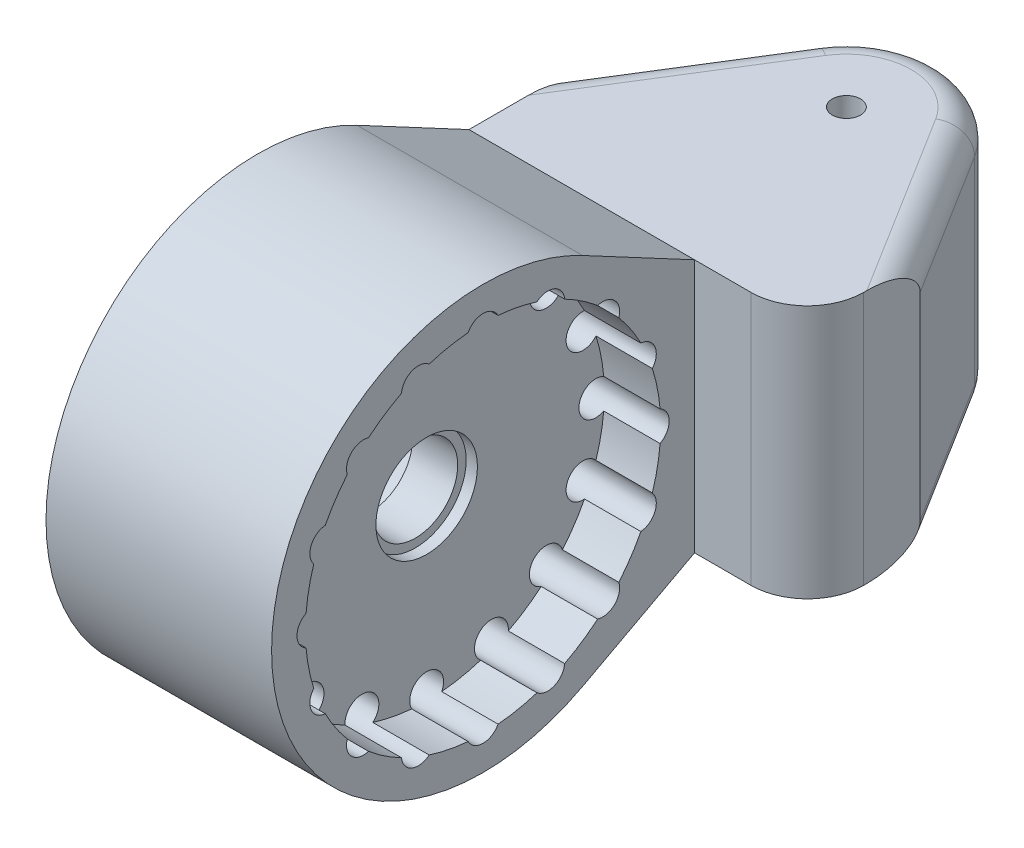
SolidWorks part; units mm, degrees
material "ABS"
ref_plane "Front Plane" through (0, 0, 0) normal (0, 0, 1) x (1, 0, 0)
ref_plane "Top Plane" through (0, 0, 0) normal (0, 1, 0) x (1, 0, 0)
ref_plane "Right Plane" through (0, 0, 0) normal (1, 0, 0) x (0, 0, -1)
ref_plane "Plane1" through (0, 0, 36.9266) normal (0, 0, 1) x (1, 0, 0)
sketch "Sketch1" plane through (0, 0, 0) normal (0, 0, 1) x (1, 0, 0)
  line L1 (-30, 22.5) -> (30, 22.5)
  line L2 (-30, 22.5) -> (-30, -22.5)
  line L3 (-30, -22.5) -> (30, -22.5)
  line L4 (30, 22.5) -> (30, -22.5)
  line L5 (-30, 22.5) -> (30, -22.5) construction
  line L6 (-30, -22.5) -> (30, 22.5) construction
  point P0 (0, 0)
  dimension "D1" = 45
  dimension "D2" = 60
extrude "Boss-Extrude1" add sketch "Sketch1" along normal blind 20 from surface at 36.9266 starting at plane "Plane1"
sketch "Sketch2" plane through (0, 0, 56.9266) normal (0, 0, 1) x (1, 0, 0)
  line L0 (-30, 22.5) -> (30, 22.5) construction
  line L1 (-30, -22.5) -> (0, -22.5)
  line L2 (-30, -22.5) -> (-30, 22.5)
  line L3 (-30, 22.5) -> (0, 22.5)
  line L4 (0, -22.5) -> (0, 22.5)
extrude "Boss-Extrude2" add sketch "Sketch2" along normal blind 75
sketch "Sketch4" plane through (0, -22.5, 0) normal (0, -1, 0) x (1, 0, 0)
  line L0 (30, 36.9266) -> (-30, 36.9266) construction
  line L1 (-30, 36.9266) -> (-14.001, 11.2694)
  line L2 (30, 36.9266) -> (14.001, 11.2694)
  line L3 (-30, 36.9266) -> (30, 36.9266)
  arc A0 (-14.001, 11.2694) -> (14.001, 11.2694) centre (0, 20) ccw
  circle A1 centre (0, 20) radius 2.5
  dimension "D2" = 5
  dimension "D3" = 16.5
  dimension "D1" = 16.9266
extrude "Boss-Extrude3" add sketch "Sketch4" against normal up to surface (45 mm away) up to face at (0, 22.5, 75.2599)
fillet "Fillet1" radius 5 6 edges at (-22.0005, 22.5, 24.098) (-22.0005, -22.5, 24.098) (22.0005, 22.5, 24.098) (22.0005, -22.5, 24.098) (0, 22.5, 3.5) (0, -22.5, 3.5)
sketch "Sketch5" plane through (0, 0, 0) normal (1, 0, 0) x (0, 0, -1)
  line L0 (-94.4266, -22.5) -> (-94.4266, 22.5) construction
  line L1 (-131.9266, -22.5) -> (-56.9266, -22.5) construction
  line L2 (-131.9266, 22.5) -> (-56.9266, 22.5) construction
  line L3 (-56.9266, -22.5) -> (-56.9266, 22.5) construction
  line L4 (-56.9266, -22.5) -> (-76.7795, -33.0882)
  line L5 (-76.7795, 33.0882) -> (-56.9266, 22.5)
  line L6 (-56.9266, -22.5) -> (-56.9266, 22.5)
  arc A0 (-76.7795, 33.0882) -> (-76.7795, -33.0882) centre (-94.4266, 0) ccw
  dimension "D1" = 37.5
extrude "Boss-Extrude4" add sketch "Sketch5" against normal through all
sketch "Sketch6" plane through (0, 0, 0) normal (1, 0, 0) x (0, 0, -1)
  line L0 (-94.4266, -43.7321) -> (-94.4266, -37.5)
  line L1 (-94.4266, 37.5) -> (-94.4266, 43.7321)
  arc A1 (-94.4266, 43.7321) -> (-94.4266, -43.7321) centre (-94.4266, 0) ccw
  arc A2 (-124.4266, -22.5) -> (-76.7795, -33.0882) centre (-94.4266, 0) ccw construction
  arc A3 (-124.4266, -22.5) -> (-94.4266, -37.5) centre (-94.4266, 0) ccw construction
  arc A4 (-94.4266, 37.5) -> (-94.4266, -37.5) centre (-94.4266, 0) ccw
extrude "Cut-Extrude1" cut sketch "Sketch6" against normal up to next
sketch "Sketch9" plane through (0, 0, 0) normal (1, 0, 0) x (0, 0, -1)
  line L3 (-76.7795, -33.0882) -> (-56.9266, -22.5)
  line L4 (-56.9266, -22.5) -> (-56.9266, 22.5)
  line L5 (-56.9266, 22.5) -> (-76.7795, 33.0882)
  line L6 (-76.7795, -33.0882) -> (-56.9266, -22.5) construction
  line L7 (-56.9266, -22.5) -> (-56.9266, 22.5) construction
  line L8 (-56.9266, 22.5) -> (-76.7795, 33.0882) construction
  circle A0 centre (-94.4266, 0) radius 30 construction
  arc A1 (-76.7795, 33.0882) -> (-76.7795, -33.0882) centre (-94.4266, 0) ccw
  arc A2 (-76.7795, 33.0882) -> (-76.7795, -33.0882) centre (-94.4266, 0) ccw construction
  circle A3 centre (-94.4266, -30) radius 3
  circle A4 centre (-105.9071, -27.7164) radius 3
  circle A5 centre (-115.6398, -21.2132) radius 3
  circle A6 centre (-122.143, -11.4805) radius 3
  circle A7 centre (-124.4266, 0) radius 3
  circle A8 centre (-122.143, 11.4805) radius 3
  circle A9 centre (-115.6398, 21.2132) radius 3
  circle A10 centre (-105.9071, 27.7164) radius 3
  circle A11 centre (-94.4266, 30) radius 3
  circle A12 centre (-82.9461, 27.7164) radius 3
  circle A13 centre (-73.2134, 21.2132) radius 3
  circle A14 centre (-66.7102, 11.4805) radius 3
  circle A15 centre (-64.4266, 0) radius 3
  circle A16 centre (-66.7102, -11.4805) radius 3
  circle A17 centre (-73.2134, -21.2132) radius 3
  circle A18 centre (-82.9461, -27.7164) radius 3
  point P39 (-94.4266, 0)
  dimension "D2" = 6
  dimension "D4" = 60
extrude "Cut-Extrude2" cut sketch "Sketch9" against normal blind 10
sketch "Sketch10" plane through (0, 0, 0) normal (1, 0, 0) x (0, 0, -1)
  line L3 (-76.7795, -33.0882) -> (-56.9266, -22.5)
  line L4 (-56.9266, -22.5) -> (-56.9266, 22.5)
  line L5 (-56.9266, 22.5) -> (-76.7795, 33.0882)
  line L6 (-76.7795, -33.0882) -> (-56.9266, -22.5)
  line L7 (-56.9266, -22.5) -> (-56.9266, 22.5)
  line L8 (-56.9266, 22.5) -> (-76.7795, 33.0882)
  arc A1 (-79.9577, -27.9804) -> (-74.1131, -24.0751) centre (-94.4266, 0) ccw
  arc A2 (-76.7795, 33.0882) -> (-76.7795, -33.0882) centre (-94.4266, 0) ccw construction
  arc A3 (-108.8955, -27.9804) -> (-103.9807, -30.0162) centre (-105.9071, -27.7164) ccw
  circle A4 centre (-94.4266, -30) radius 3
  arc A5 (-97.0864, -31.3875) -> (-91.7667, -31.3875) centre (-94.4266, -30) ccw
  arc A6 (-118.5017, -20.3135) -> (-114.7401, -24.0751) centre (-115.6398, -21.2132) ccw
  arc A7 (-124.4427, -9.5541) -> (-122.407, -14.4689) centre (-122.143, -11.4805) ccw
  arc A8 (-125.8141, 2.6599) -> (-125.8141, -2.6599) centre (-124.4266, 0) ccw
  arc A9 (-122.407, 14.4689) -> (-124.4427, 9.5541) centre (-122.143, 11.4805) ccw
  arc A10 (-114.7401, 24.0751) -> (-118.5017, 20.3135) centre (-115.6398, 21.2132) ccw
  arc A11 (-103.9807, 30.0162) -> (-108.8955, 27.9804) centre (-105.9071, 27.7164) ccw
  arc A12 (-91.7667, 31.3875) -> (-97.0864, 31.3875) centre (-94.4266, 30) ccw
  arc A13 (-79.9577, 27.9804) -> (-84.8725, 30.0162) centre (-82.9461, 27.7164) ccw
  arc A14 (-70.3515, 20.3135) -> (-74.1131, 24.0751) centre (-73.2134, 21.2132) ccw
  arc A15 (-64.4104, 9.5541) -> (-66.4462, 14.4689) centre (-66.7102, 11.4805) ccw
  arc A16 (-63.0391, -2.6599) -> (-63.0391, 2.6599) centre (-64.4266, 0) ccw
  arc A17 (-66.4462, -14.4689) -> (-64.4104, -9.5541) centre (-66.7102, -11.4805) ccw
  arc A18 (-74.1131, -24.0751) -> (-70.3515, -20.3135) centre (-73.2134, -21.2132) ccw
  arc A19 (-84.8725, -30.0162) -> (-79.9577, -27.9804) centre (-82.9461, -27.7164) ccw
  arc A20 (-91.7667, -31.3875) -> (-84.8725, -30.0162) centre (-94.4266, 0) ccw
  arc A21 (-103.9807, -30.0162) -> (-97.0864, -31.3875) centre (-94.4266, 0) ccw
  arc A22 (-114.7401, -24.0751) -> (-108.8955, -27.9804) centre (-94.4266, 0) ccw
  arc A23 (-122.407, -14.4689) -> (-118.5017, -20.3135) centre (-94.4266, 0) ccw
  arc A24 (-125.8141, -2.6599) -> (-124.4427, -9.5541) centre (-94.4266, 0) ccw
  arc A25 (-124.4427, 9.5541) -> (-125.8141, 2.6599) centre (-94.4266, 0) ccw
  arc A26 (-118.5017, 20.3135) -> (-122.407, 14.4689) centre (-94.4266, 0) ccw
  arc A27 (-108.8955, 27.9804) -> (-114.7401, 24.0751) centre (-94.4266, 0) ccw
  arc A28 (-97.0864, 31.3875) -> (-103.9807, 30.0162) centre (-94.4266, 0) ccw
  arc A29 (-84.8725, 30.0162) -> (-91.7667, 31.3875) centre (-94.4266, 0) ccw
  arc A30 (-74.1131, 24.0751) -> (-79.9577, 27.9804) centre (-94.4266, 0) ccw
  arc A31 (-66.4462, 14.4689) -> (-70.3515, 20.3135) centre (-94.4266, 0) ccw
  arc A32 (-63.0391, 2.6599) -> (-64.4104, 9.5541) centre (-94.4266, 0) ccw
  arc A33 (-64.4104, -9.5541) -> (-63.0391, -2.6599) centre (-94.4266, 0) ccw
  arc A34 (-70.3515, -20.3135) -> (-66.4462, -14.4689) centre (-94.4266, 0) ccw
  arc A36 (-76.7795, 33.0882) -> (-76.7795, -33.0882) centre (-94.4266, 0) ccw
  arc A37 (-76.7795, 33.0882) -> (-76.7795, -33.0882) centre (-94.4266, 0) ccw
  point P41 (-94.4266, 0)
  dimension "D1" = 6
  dimension "D2" = 0
  dimension "D3" = 0
extrude "Boss-Extrude5" add sketch "Sketch10" along normal blind 10
sketch "Sketch11" plane through (0, 0, 0) normal (1, 0, 0) x (0, 0, -1)
  circle A1 centre (-94.4266, 0) radius 7.5
  dimension "D1" = 15
extrude "Cut-Extrude3" cut sketch "Sketch11" against normal through all
sketch "Sketch12" plane through (0, 0, 0) normal (1, 0, 0) x (0, 0, -1)
  circle A0 centre (-94.4266, 0) radius 9
  dimension "D1" = 18
extrude "Cut-Extrude4" cut sketch "Sketch12" against normal blind 2
sketch "Sketch13" plane through (-30, 0, 0) normal (-1, 0, 0) x (0, 0, 1)
  circle A0 centre (94.4266, 0) radius 25
  dimension "D1" = 50
extrude "Cut-Extrude5" cut sketch "Sketch13" against normal blind 20
fillet "Fillet2" radius 10 1 edges at (30, 0, 56.9266)
equation "\"Mounting Leg Thickness\"=20"
equation "\"D1@Boss-Extrude1\"=\"Mounting Leg Thickness\""
equation "\"Hole Diameter\"=5"
equation "\"D2@Sketch4\"=\"Hole Diameter\""
equation "\"Pin Diameter\"=6"
equation "\"D2@Sketch9\"=\"Pin Diameter\""
